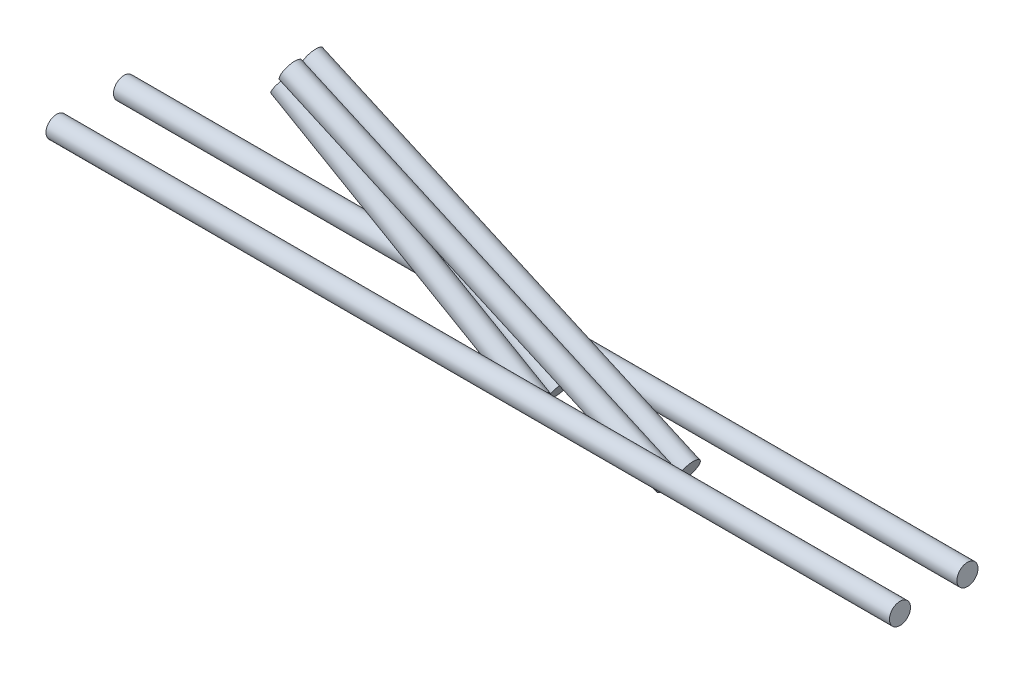
SolidWorks part; units mm, degrees
ref_plane "前视基准面" through (0, 0, 0) normal (0, 0, 1) x (1, 0, 0)
ref_plane "上视基准面" through (0, 0, 0) normal (0, 1, 0) x (1, 0, 0)
ref_plane "右视基准面" through (0, 0, 0) normal (1, 0, 0) x (0, 0, -1)
sketch "草图1" plane through (0, 0, 0) normal (0, 1, 0) x (1, 0, 0)
  line L0 (-42.256, 0) -> (66.5921, 0) construction
  line L2 (70.6764, 8) -> (170.6764, 8)
ref_plane "基准面1" through (170.6764, 0, -8) normal (1, 0, 0) x (0, 0, -1)
sketch "草图2" plane through (170.6764, 0, -8) normal (1, 0, 0) x (0, 0, -1)
  circle A0 centre (-0.3916, 0) radius 2.5
sweep "扫描1" add profiles "草图2" path "草图1"
sketch "草图3" plane through (170.6764, 0, 0) normal (1, 0, 0) x (0, 0, -1)
  line L0 (7.6084, 0) -> (-8.3916, 0) construction
  circle A0 centre (-8.3916, 0) radius 2.5
  dimension "D1" = 16
extrude "凸台-拉伸1" add sketch "草图3" against normal blind 100 and the other way blind 100 separate body
sketch "草图5" plane through (170.6764, 0, 0) normal (1, 0, 0) x (0, 0, -1)
  circle A0 centre (7.6084, 0) radius 2.5
extrude "凸台-拉伸3" add sketch "草图5" along normal blind 100
sketch "草图6" plane through (170.6764, 0, -8) normal (1, 0, 0) x (0, 0, -1)
  line L0 (11.0158, 0) -> (-35.338, 0) construction
ref_plane "基准面2" through (128.0073, -73.9051, 0) normal (-0.866, 0.5, 0) x (0, 0, -1)
sketch "草图9" plane through (128.0073, -73.9051, 0) normal (-0.866, 0.5, 0) x (0, 0, -1)
  line L0 (5.1841, -85.2896) -> (-5.8159, -85.2896)
  circle A0 centre (2.1841, -85.2896) radius 2.5
  circle A1 centre (-2.8159, -85.2896) radius 2.5
  dimension "D3" = 5
  dimension "D4" = 5
  dimension "D1" = 3
  dimension "D2" = 3
extrude "凸台-拉伸4" add sketch "草图9" along normal blind 60 and the other way blind 10 separate body contours L0 A1 | L0 A1 | L0 A0 | L0 A0 region at (171.1826, 0.8768, -2.1841) region at (170.1216, -0.961, -2.1841) region at (171.1826, 0.8768, 2.8159) region at (170.1216, -0.961, 2.8159)
sketch "草图11" plane through (0, 0, 0) normal (0, 0, 1) x (1, 0, 0)
  line L0 (119.4919, 34.3536) -> (196.4269, 0)
ref_plane "基准面3" through (196.4269, 0, 0) normal (0.9131, -0.4077, 0) x (0, 0, -1)
sketch "草图12" plane through (196.4269, 0, 0) normal (0.9131, -0.4077, 0) x (0, 0, -1)
  line L0 (0, 1.7931) -> (0, -1.6841) construction
  line L1 (5.1084, 0.0545) -> (-5.8916, 0.0545) construction
  line L2 (5.1084, 30.2734) -> (5.1084, -51.2717) construction
  line L3 (-5.8916, -51.2717) -> (-5.8916, 30.2734) construction
  circle A0 centre (2.1084, 0.0545) radius 2.5
  circle A1 centre (-2.8916, 0.0545) radius 2.5
  dimension "D3" = 5
  dimension "D4" = 5
  dimension "D1" = 3
  dimension "D2" = 3
extrude "凸台-拉伸5" add sketch "草图12" along normal blind 15 and the other way blind 83 contours A1 | A0 region at (196.4491, 0.0497, -2.1084) region at (196.4491, 0.0497, 2.8916)
